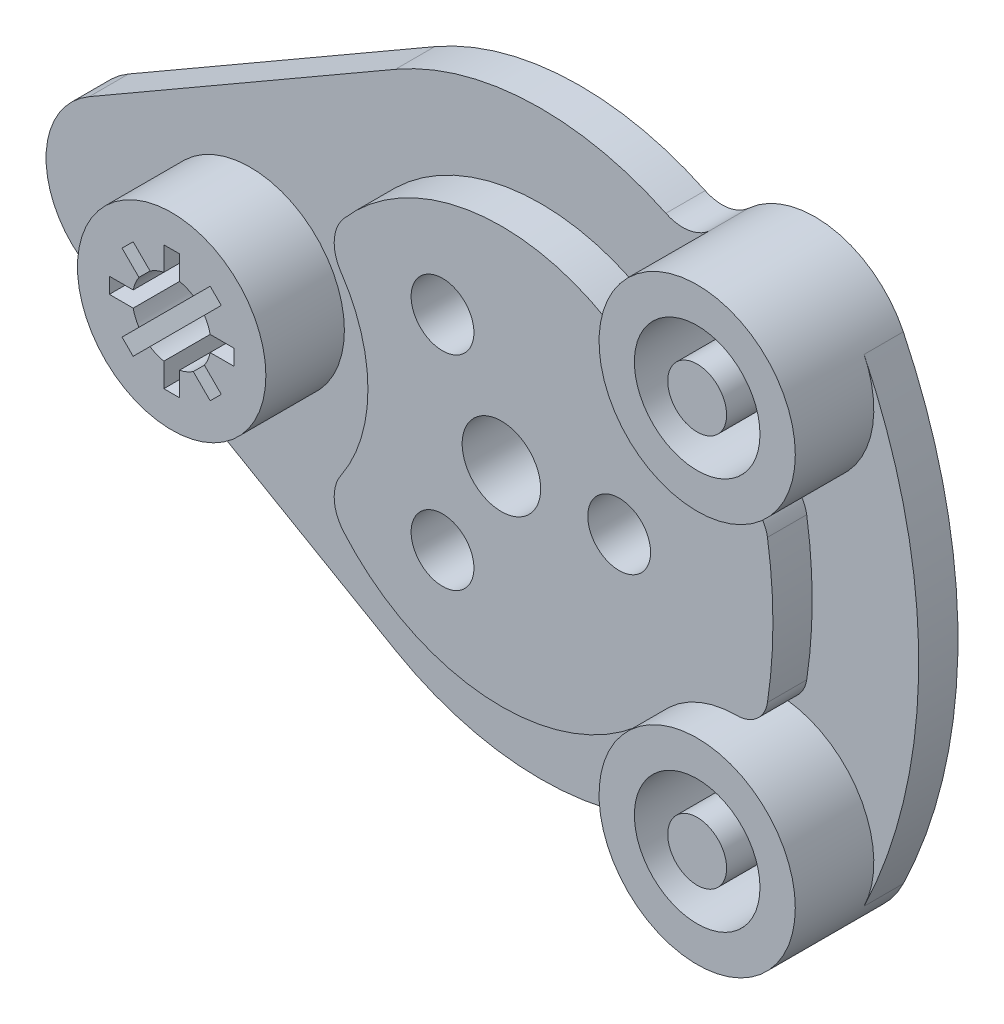
SolidWorks part; units mm, degrees
note: The reader was unsure of these and kept them because the rebuilt part matched: shared geometry of "Эскиз1<3>", "Эскиз1<4>".
ref_plane "Спереди" through (0, 0, 0) normal (0, 0, 1) x (1, 0, 0)
ref_plane "Сверху" through (0, 0, 0) normal (0, 1, 0) x (1, 0, 0)
ref_plane "Справа" through (0, 0, 0) normal (1, 0, 0) x (0, 0, -1)
sketch "Эскиз1" plane through (0, 0, 0) normal (0, 0, 1) x (1, 0, 0)
  line L0 (-148, 0) -> (184.5808, 0) construction
  line L1 (0, 94.5636) -> (0, -116.0893) construction
  line L2 (-115, 19.0526) -> (-37, 64.0859)
  line L3 (-115, -19.0526) -> (-37, -64.0859)
  line L4 (59.8665, 102.8742) -> (59.8665, -105.8882) construction
  line L5 (-86.6392, 9.8108) -> (-82.3424, 5.514)
  line L6 (-89.8745, -2) -> (-83.798, -2)
  line L7 (-89.8745, -2) -> (-89.8745, 2)
  line L8 (-89.8745, 2) -> (-83.798, 2)
  line L9 (-83.798, -2) -> (-83.798, 2)
  line L10 (-89.8745, -2) -> (-83.798, 2) construction
  line L11 (-89.8745, 2) -> (-83.798, -2) construction
  line L12 (-86.6392, 9.8108) -> (-83.8108, 12.6392)
  line L13 (-83.8108, 12.6392) -> (-79.514, 8.3424)
  line L14 (-82.3424, 5.514) -> (-79.514, 8.3424)
  line L15 (-86.6392, 9.8108) -> (-79.514, 8.3424) construction
  line L16 (-83.8108, 12.6392) -> (-82.3424, 5.514) construction
  line L17 (-76, 15.8745) -> (-76, 9.798)
  line L18 (-76, 15.8745) -> (-72, 15.8745)
  line L19 (-72, 15.8745) -> (-72, 9.798)
  line L20 (-76, 9.798) -> (-72, 9.798)
  line L21 (-76, 15.8745) -> (-72, 9.798) construction
  line L22 (-72, 15.8745) -> (-76, 9.798) construction
  line L23 (-64.1892, 12.6392) -> (-68.486, 8.3424)
  line L24 (-64.1892, 12.6392) -> (-61.3608, 9.8108)
  line L25 (-61.3608, 9.8108) -> (-65.6576, 5.514)
  line L26 (-68.486, 8.3424) -> (-65.6576, 5.514)
  line L27 (-64.1892, 12.6392) -> (-65.6576, 5.514) construction
  line L28 (-61.3608, 9.8108) -> (-68.486, 8.3424) construction
  line L29 (-58.1255, 2) -> (-64.202, 2)
  line L30 (-58.1255, 2) -> (-58.1255, -2)
  line L31 (-58.1255, -2) -> (-64.202, -2)
  line L32 (-64.202, 2) -> (-64.202, -2)
  line L33 (-58.1255, 2) -> (-64.202, -2) construction
  line L34 (-58.1255, -2) -> (-64.202, 2) construction
  line L35 (-61.3608, -9.8108) -> (-65.6576, -5.514)
  line L36 (-61.3608, -9.8108) -> (-64.1892, -12.6392)
  line L37 (-64.1892, -12.6392) -> (-68.486, -8.3424)
  line L38 (-65.6576, -5.514) -> (-68.486, -8.3424)
  line L39 (-61.3608, -9.8108) -> (-68.486, -8.3424) construction
  line L40 (-64.1892, -12.6392) -> (-65.6576, -5.514) construction
  line L41 (-72, -15.8745) -> (-72, -9.798)
  line L42 (-72, -15.8745) -> (-76, -15.8745)
  line L43 (-76, -15.8745) -> (-76, -9.798)
  line L44 (-72, -9.798) -> (-76, -9.798)
  line L45 (-72, -15.8745) -> (-76, -9.798) construction
  line L46 (-76, -15.8745) -> (-72, -9.798) construction
  line L47 (-83.8108, -12.6392) -> (-79.514, -8.3424)
  line L48 (-83.8108, -12.6392) -> (-86.6392, -9.8108)
  line L49 (-86.6392, -9.8108) -> (-82.3424, -5.514)
  line L50 (-79.514, -8.3424) -> (-82.3424, -5.514)
  line L51 (-83.8108, -12.6392) -> (-82.3424, -5.514) construction
  line L52 (-86.6392, -9.8108) -> (-79.514, -8.3424) construction
  circle A0 centre (0, 0) radius 10
  circle A1 centre (30, 0) radius 8
  arc A2 (-37, -64.0859) -> (31.8993, -66.7715) centre (0, 0) ccw
  circle A3 centre (-15, -25.9808) radius 8
  circle A4 centre (-74, 0) radius 24
  circle A5 centre (-15, 25.9808) radius 8
  arc A6 (-40.8811, -22.4307) -> (-40.8811, 22.4307) centre (-74, 0) ccw
  arc A7 (-40.8811, 22.4307) -> (-40.1831, 34.559) centre (-32.6014, 28.0384) cw
  arc A8 (-40.1831, -34.559) -> (-40.8811, -22.4307) centre (-32.6014, -28.0384) cw
  arc A9 (-40.1831, -34.559) -> (40.6785, -33.9744) centre (0, 0) ccw
  arc A10 (-115, -19.0526) -> (-115, 19.0526) centre (-104, 0) cw
  circle A11 centre (-30, 0) radius 8 [skipped]
  circle A12 centre (15, 25.9808) radius 8 [skipped]
  circle A13 centre (15, -25.9808) radius 8 [skipped]
  circle A14 centre (59.8665, 50) radius 25
  circle A15 centre (59.8665, -50) radius 25
  arc A16 (40.6785, 33.9744) -> (-40.1831, 34.559) centre (0, 0) ccw
  arc A17 (31.8993, 66.7715) -> (-37, 64.0859) centre (0, 0) ccw
  circle A18 centre (59.8665, 50) radius 16
  circle A19 centre (59.8665, -50) radius 16
  circle A20 centre (59.8665, -50) radius 7.5
  circle A21 centre (59.8665, 50) radius 7.5
  arc A22 (67.7738, 18.2143) -> (59.8665, 25) centre (59.8665, 17) ccw
  arc A23 (67.7738, -18.2143) -> (59.8665, -25) centre (59.8665, -17) cw
  arc A24 (31.8993, 66.7715) -> (42.969, 68.4248) centre (36.21, 75.7947) ccw
  arc A25 (67.7738, -18.2143) -> (67.7738, 18.2143) centre (-50.8358, 0) ccw
  arc A26 (42.969, -68.4248) -> (31.8993, -66.7715) centre (36.21, -75.7947) ccw
  arc A27 (82.3799, -60.8696) -> (82.3799, 60.8696) centre (-43.6951, 0) ccw
  arc A28 (-58.1255, 2) -> (-89.8745, 2) centre (-74, 0) ccw construction
  arc A29 (-83.798, -2) -> (-82.3424, -5.514) centre (-74, 0) ccw
  arc A30 (-68.486, 8.3424) -> (-79.514, 8.3424) centre (-74, 0) ccw
  arc A31 (-64.202, 2) -> (-65.6576, 5.514) centre (-74, 0) ccw
  arc A32 (-65.6576, -5.514) -> (-64.202, -2) centre (-74, 0) ccw
  arc A33 (-72, -9.798) -> (-68.486, -8.3424) centre (-74, 0) ccw
  arc A34 (-79.514, -8.3424) -> (-76, -9.798) centre (-74, 0) ccw
  arc A35 (-82.3424, 5.514) -> (-83.798, 2) centre (-74, 0) ccw
  point P22 (0, 0)
  point P26 (0, 0)
  point P64 (-86.8362, 0)
  point P71 (-83.0766, 9.0766)
  point P76 (-74, 12.8362)
  point P81 (-64.9234, 9.0766)
  point P86 (-61.1638, 0)
  point P91 (-64.9234, -9.0766)
  point P96 (-74, -12.8362)
  point P101 (-83.0766, -9.0766)
  point P106 (-74, 0)
  dimension "D1" = 20
  dimension "D2" = 16
  dimension "D5" = 106
  dimension "D6" = 148
  dimension "D8" = 48
  dimension "D10" = 40
  dimension "D11" = 10
  dimension "D12" = 10
  dimension "D13" = 22
  dimension "D14" = 50
  dimension "D16" = 32
  dimension "D17" = 15
  dimension "D18" = 8
  dimension "D19" = 120
  dimension "D20" = 100
  dimension "D21" = 10
  dimension "D22" = 10
  dimension "D15" = 140
  dimension "D23" = 32
  dimension "D24" = 20
  dimension "D3" = 30
  dimension "D7" = 148
  dimension "D9" = 74
  dimension "D25" = 4
  dimension "D4" = 6
  dimension "D26" = 8
extrude "Бобышка-Вытянуть1" add sketch "Эскиз1" along normal blind 10 contours A26 A15 A9 A8 A6 A7 A16 A14 A24 A17 L2 A10 L3 A2 A4 | A15 A27 A14 A22 A25 A23 | A19 A20 | A18 A21
extrude "Бобышка-Вытянуть2" add sketch "Эскиз1<3>" along normal blind 20 contours A23 A25 A22 A14 A16 A7 A6 A8 A9 A15 A5 A3 A1 A0
sketch "Эскиз1<3>" plane through (0, 0, 0) normal (0, 0, 1) x (1, 0, 0) same geometry as "Эскиз1"
extrude "Бобышка-Вытянуть3" add sketch "Эскиз1<4>" along normal blind 30 contours A4 A35 L5 L12 L13 A30 L17 L18 L19 L23 L24 L25 A31 L29 L30 L31 A32 L35 L36 L37 A33 L41 L42 L43 A34 L47 L48 L49 A29 L6 L7 L8 | A15 A19 | A21 | A14 A18 | A20
sketch "Эскиз1<4>" plane through (0, 0, 0) normal (0, 0, 1) x (1, 0, 0) same geometry as "Эскиз1"
